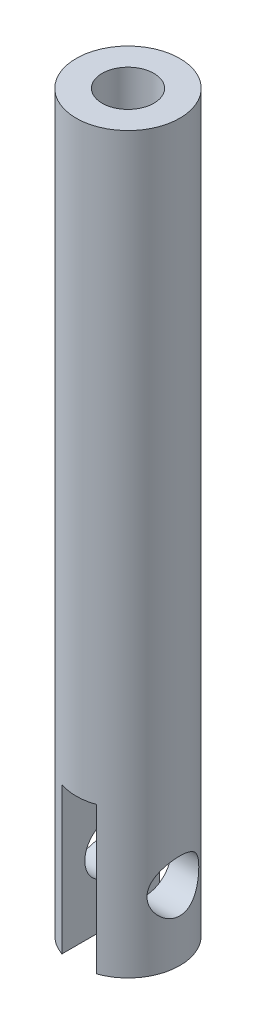
SolidWorks part; units mm, degrees
material "ABS"
ref_plane "Front" through (0, 0, 0) normal (0, 0, 1) x (1, 0, 0)
ref_plane "Top" through (0, 0, 0) normal (0, 1, 0) x (1, 0, 0)
ref_plane "Right" through (0, 0, 0) normal (1, 0, 0) x (0, 0, -1)
sketch "Sketch1" plane through (0, 0, 0) normal (0, 1, 0) x (1, 0, 0)
  circle A0 centre (0, 0) radius 6
  circle A1 centre (0, 0) radius 1.5
  dimension "D1" = 12
  dimension "D2" = 3
extrude "Boss-Extrude1" add sketch "Sketch1" along normal blind 75
sketch "Sketch2" plane through (0, 0, 0) normal (0, 0, 1) x (1, 0, 0)
  line L0 (-1657.5786, 28) -> (-1730.2517, 28) construction
  line L1 (-388.9039, 49.5) -> (-461.5771, 49.5) construction
  circle A0 centre (0, 23.5) radius 1.5
  circle A1 centre (0, 54) radius 1.5
  point P8 (-425.2405, 49.5)
  dimension "D1" = 4.5
  dimension "D2" = 4.5
  dimension "D3" = 3
  dimension "D4" = 3
extrude "Cut-Extrude1" cut sketch "Sketch2" against normal blind 75
sketch "Sketch3" plane through (0, 0, 0) normal (0, 0, 1) x (1, 0, 0)
  point P0 (0, 54)
  point P1 (0, 23.5)
sketch "Sketch4" plane through (0, 0, 0) normal (0, -1, 0) x (1, 0, 0)
  circle A0 centre (0, 0) radius 1.5
  circle A1 centre (0, 0) radius 6
  circle A2 centre (0, 0) radius 6
  dimension "D1" = 0
extrude "Boss-Extrude2" add sketch "Sketch4" along normal blind 10
sketch "Sketch5" plane through (0, -10, 0) normal (0, -1, 0) x (1, 0, 0)
  line L0 (1.0917, 9.1547) -> (8.88, -2.479) construction
  line L1 (2, -13.7728) -> (-2, -13.7728)
  line L2 (2, -13.7728) -> (2, 13.7728)
  line L3 (2, 13.7728) -> (-2, 13.7728)
  line L4 (-2, -13.7728) -> (-2, 13.7728)
  line L5 (2, -13.7728) -> (-2, 13.7728) construction
  line L6 (2, 13.7728) -> (-2, -13.7728) construction
  point P0 (0, 0)
  dimension "D1" = 4
extrude "Cut-Extrude2" cut sketch "Sketch5" against normal blind 17
sketch "Sketch7" plane through (-2, 0, 0) normal (1, 0, 0) x (0, 0, -1)
  line L0 (-5.6569, -10) -> (5.6569, -10) construction
  circle A0 centre (0, -2) radius 3
  point P4 (0, -10)
  dimension "D1" = 8
  dimension "D2" = 6
extrude "Cut-Extrude4" cut sketch "Sketch7" against normal blind 15 and the other way blind 15
sketch "Sketch8" plane through (0, 75, 0) normal (0, 1, 0) x (1, 0, 0)
  circle A0 centre (0, 0) radius 3
  dimension "D1" = 6
extrude "Cut-Extrude5" cut sketch "Sketch8" against normal blind 14
